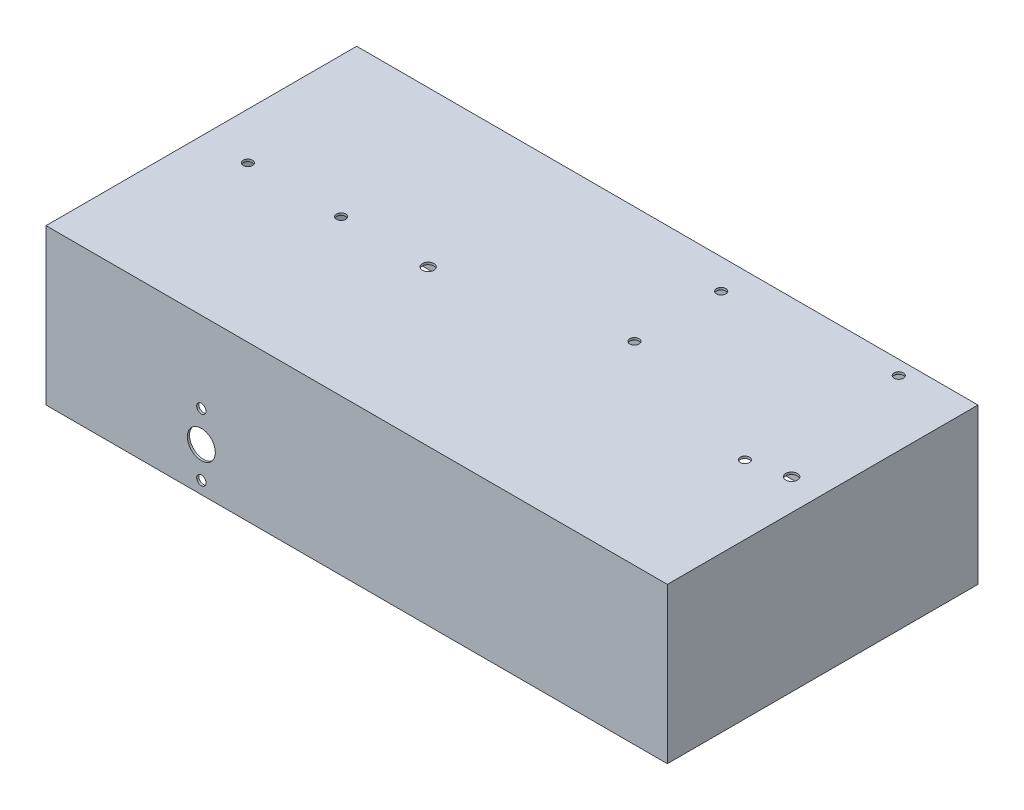
SolidWorks part; units mm, degrees
ref_plane "Front Plane" through (0, 0, 0) normal (0, 0, 1) x (1, 0, 0)
ref_plane "Top Plane" through (0, 0, 0) normal (0, 1, 0) x (1, 0, 0)
ref_plane "Right Plane" through (0, 0, 0) normal (1, 0, 0) x (0, 0, -1)
sketch "Sketch1" plane through (0, 0, 0) normal (0, 1, 0) x (1, 0, 0)
  line L1 (0, 50) -> (200, 50)
  line L2 (0, 50) -> (0, -50)
  line L3 (0, -50) -> (200, -50)
  line L4 (200, 50) -> (200, -50)
  point P4 (0, 0)
  dimension "D1" = 200
  dimension "D2" = 100
extrude "Boss-Extrude1" add sketch "Sketch1" along normal blind 50
sketch "Sketch2" plane through (0, 0, 50) normal (0, 0, 1) x (1, 0, 0)
  line L0 (0, 50) -> (0, 0) construction
  line L1 (50, 24) -> (50, 4) construction
  line L2 (0, 50) -> (200, 50) construction
  circle A0 centre (50, 14) radius 4.5
  circle A1 centre (50, 4) radius 1.5
  circle A2 centre (50, 24) radius 1.5
  point P0 (50, 14)
  point P9 (50, 14)
  dimension "D3" = 9
  dimension "D4" = 3
  dimension "D1" = 50
  dimension "D2" = 36
  dimension "D5" = 20
sketch "Sketch3" plane through (0, 0, 0) normal (0, -1, 0) x (1, 0, 0)
  line L0 (0.7, 49.3) -> (0.7, -49.3)
  line L1 (0.7, -49.3) -> (199.3, -49.3)
  line L2 (199.3, -49.3) -> (199.3, 49.3)
  line L3 (199.3, 49.3) -> (0.7, 49.3)
  line L4 (0, 50) -> (0, -50)
  line L5 (0, -50) -> (200, -50)
  line L6 (200, -50) -> (200, 50)
  line L7 (200, 50) -> (0, 50)
  line L8 (0, 50) -> (0, -50) construction
  line L9 (0, -50) -> (200, -50) construction
  line L10 (200, -50) -> (200, 50) construction
  line L11 (200, 50) -> (0, 50) construction
  dimension "D1" = 0
  dimension "D2" = 0.7
extrude "Cut-Extrude1" cut sketch "Sketch3" against normal offset from surface (49.3 mm away) 0.7 up to face at (100, 50, 0)
sketch "Sketch4" plane through (0, 0, 0) normal (0, -1, 0) x (1, 0, 0)
  line L0 (0.7, -49.3) -> (199.3, -49.3) construction
  line L1 (145, -49.3) -> (199.3, -49.3)
  line L2 (145, -49.3) -> (145, 49.3)
  line L3 (145, 49.3) -> (199.3, 49.3)
  line L4 (199.3, -49.3) -> (199.3, 49.3)
  line L5 (199.3, 49.3) -> (0.7, 49.3) construction
  line L6 (160, -47.9) -> (160, 49.3) construction
  line L7 (200, -50) -> (200, 50) construction
  line L8 (199.3, -49.3) -> (199.3, 49.3) construction
  circle A0 centre (160, 0.7) radius 11.43 construction
  point P12 (160, 0.7)
  dimension "D3" = 22.86
  dimension "D1" = 40
  dimension "D2" = 55
  dimension "D4" = 50
extrude "Boss-Extrude2" add sketch "Sketch4" against normal blind 0.7
extrude "Cut-Extrude2" cut sketch "Sketch2" against normal through all
sketch "Sketch6" plane through (0, 0, 50) normal (0, 0, 1) x (1, 0, 0)
  line L0 (4.6, 50) -> (4.6, 0) construction
  line L1 (0, 50) -> (200, 50) construction
  line L2 (200, 0) -> (0, 0) construction
  line L3 (0, 45) -> (200, 45) construction
  line L4 (0, 50) -> (0, 0) construction
  line L5 (200, 50) -> (200, 0) construction
  line L6 (0, 35) -> (200, 35) construction
  line L7 (54.1, 45) -> (54.1, 35) construction
  line L8 (69.1, 45) -> (69.1, 35) construction
  circle A0 centre (4.6, 45) radius 1.5
  circle A1 centre (4.6, 35) radius 1.5
  circle A2 centre (54.1, 45) radius 1.5
  circle A3 centre (54.1, 35) radius 1.5
  circle A4 centre (69.1, 45) radius 1.5
  circle A5 centre (69.1, 35) radius 1.5
  dimension "D1" = 3
  dimension "D3" = 5
  dimension "D4" = 10
  dimension "D5" = 4.6
  dimension "D6" = 15
  dimension "D7" = 54.1
extrude "Cut-Extrude3" [suppressed] cut sketch "Sketch6" against normal up to surface (0.7 mm away) up to face at (51.5, 4, 49.3)
sketch "Sketch7" plane through (0, 0, 0) normal (-1, 0, 0) x (0, 0, 1)
  line L0 (42, 50) -> (42, 0) construction
  line L1 (-50, 50) -> (50, 50) construction
  line L2 (-50, 0) -> (50, 0) construction
  circle A0 centre (42, 45) radius 1.5
  circle A1 centre (42, 35) radius 1.5
  dimension "D4" = 3
  dimension "D1" = 8
  dimension "D2" = 5
  dimension "D3" = 10
extrude "Cut-Extrude4" [suppressed] cut sketch "Sketch7" against normal up to surface (0.7 mm away) up to face at (0.7, 24.65, 0)
sketch "Sketch8" plane through (0, 0, 0) normal (0, -1, 0) x (1, 0, 0)
  line L0 (160, -47.9) -> (160, 49.3) construction
  circle A0 centre (160, 8.45) radius 1.21
  circle A1 centre (160, -7.05) radius 1.21
  dimension "D2" = 2.42
  dimension "D1" = 7.75
  dimension "D3" = 7.75
extrude "Cut-Extrude6" cut sketch "Sketch8" against normal blind 1.8 contours A1 | A0
sketch "Sketch9" plane through (0, 50, 0) normal (0, 1, 0) x (1, 0, 0)
  line L0 (0, 0) -> (200, 0) construction
  line L1 (200, 50) -> (200, -50) construction
  circle A0 centre (15, 0) radius 1.5
  circle A1 centre (45, 0) radius 1.5
  dimension "D1" = 3
  dimension "D2" = 15
  dimension "D3" = 30
sketch "Sketch10" plane through (0, 49.3, 0) normal (0, -1, 0) x (1, 0, 0)
  line L0 (0, 0) -> (200, 0)
  line L1 (200, -50) -> (200, 50) construction
  circle A0 centre (190, 0) radius 1.87
  circle A1 centre (73, 0) radius 1.87
  dimension "D2" = 3.74
  dimension "D1" = 117
  dimension "D3" = 10
extrude "Cut-Extrude8" cut sketch "Sketch10" against normal up to surface (0.7 mm away) contours A0 | A1 up to face at (100, 50, 0)
extrude "Cut-Extrude7" cut sketch "Sketch9" against normal through all
sketch "Sketch11" plane through (0, 50, 0) normal (0, 1, 0) x (1, 0, 0)
  line L0 (193, 50) -> (193, -50) construction
  line L1 (0, 50) -> (200, 50) construction
  line L2 (200, -50) -> (0, -50) construction
  line L3 (200, 48) -> (0, 48) construction
  line L4 (200, 50) -> (200, -50) construction
  line L5 (0, -50) -> (0, 50) construction
  line L6 (126.96, 12.44) -> (126.96, 40.38) construction
  circle A0 centre (126.96, 40.38) radius 1.5
  circle A1 centre (179.03, 45.46) radius 1.5
  circle A2 centre (177.76, -2.8) radius 1.5
  circle A3 centre (126.96, 12.44) radius 1.5
  point P12 (193, 48)
  dimension "D8" = 3
  dimension "D1" = 13.97
  dimension "D2" = 66.04
  dimension "D3" = 15.24
  dimension "D4" = 2.54
  dimension "D5" = 7.62
  dimension "D6" = 50.8
  dimension "D7" = 35.56
  dimension "D9" = 7
  dimension "D10" = 2
extrude "Cut-Extrude9" cut sketch "Sketch11" against normal up to surface (0.7 mm away) up to face at (15, 49.3, 1.5)
